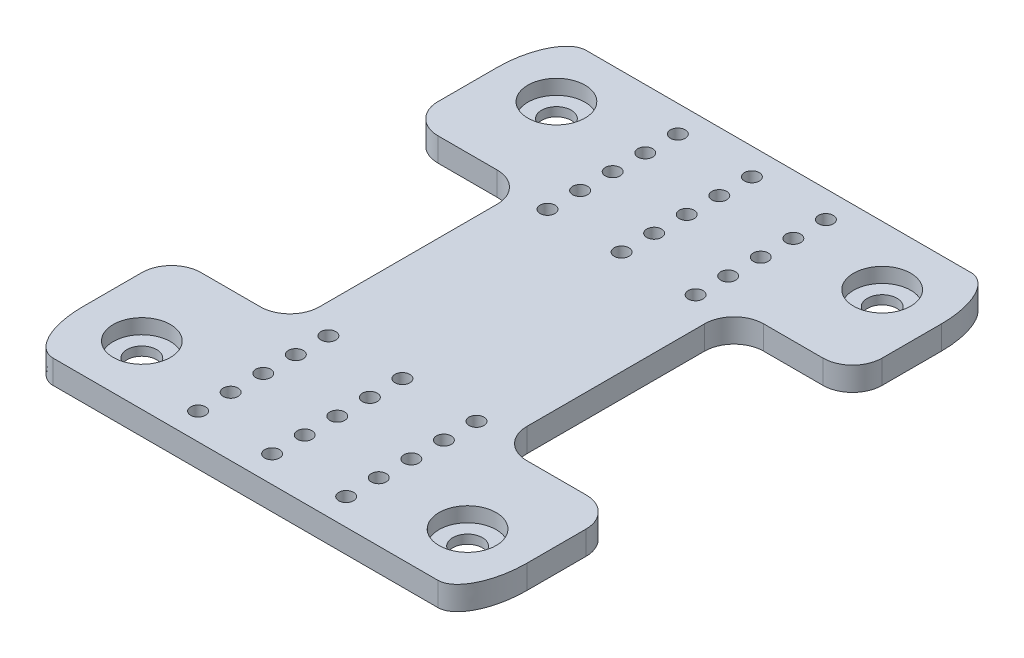
SolidWorks part; units mm, degrees
ref_plane "Front Plane" through (0, 0, 0) normal (0, 0, 1) x (1, 0, 0)
ref_plane "Top Plane" through (0, 0, 0) normal (0, 1, 0) x (1, 0, 0)
ref_plane "Right Plane" through (0, 0, 0) normal (1, 0, 0) x (0, 0, -1)
sketch "Sketch2" plane through (0, 0, 0) normal (0, 1, 0) x (1, 0, 0)
  line L1 (-75, 90) -> (75, 90)
  line L2 (-75, 90) -> (-75, -90)
  line L3 (-75, -90) -> (75, -90)
  line L4 (75, 90) -> (75, -90)
  line L5 (-75, 90) -> (75, -90) construction
  line L6 (-75, -90) -> (75, 90) construction
  point P0 (0, 0)
  dimension "D1" = 150
  dimension "D2" = 180
extrude "Boss-Extrude1" add sketch "Sketch2" along normal mid plane 8
sketch "Sketch3" plane through (0, 4, 0) normal (0, 1, 0) x (1, 0, 0)
  line L15 (-75, 90) -> (-75, -90) construction
  line L16 (-75, -90) -> (75, -90) construction
  circle A4 centre (-55, -70) radius 9.65
  dimension "D1" = 19.3
  dimension "D3" = 20
  dimension "D2" = 20
fillet "Fillet1" radius 10 2 edges at (-75, 0, -90) (75, 0, 90) second distance 20 first distance on face at (0, 0, -90) first distance on face at (0, 0, 90)
fillet "Fillet2" radius 20 2 edges at (75, 0, -90) (-75, 0, 90) second distance 10 first distance on face at (75, 1, 30) first distance on face at (-75, 1, -30)
extrude "Cut-Extrude1" cut sketch "Sketch3" against normal blind 5 contours A4
sketch "Sketch7" plane through (0, 4, 0) normal (0, 1, 0) x (1, 0, 0)
  circle A1 centre (-55, -70) radius 5
  dimension "D1" = 10
extrude "Cut-Extrude4" cut sketch "Sketch7" against normal through all
mirror "Mirror1" about plane through (0, 0, 0) normal (0, 0, 1) of "Cut-Extrude4", "Cut-Extrude1"
mirror "Mirror2" about plane through (0, 0, 0) normal (1, 0, 0) of "Cut-Extrude4", "Mirror1"
sketch "Sketch4" plane through (0, 4, 0) normal (0, 1, 0) x (1, 0, 0)
  line L0 (-75, 70) -> (-75, -70) construction
  line L1 (-115, 40) -> (-35, 40)
  line L2 (-115, 40) -> (-115, -40)
  line L3 (-115, -40) -> (-35, -40)
  line L4 (-35, 40) -> (-35, -40)
  line L5 (-115, 40) -> (-35, -40) construction
  line L6 (-115, -40) -> (-35, 40) construction
  point P0 (-75, 0)
  dimension "D1" = 80
  dimension "D2" = 40
extrude "Cut-Extrude2" cut sketch "Sketch4" against normal through all
mirror "Mirror3" about plane through (0, 0, 0) normal (1, 0, 0) of "Cut-Extrude2"
fillet "Fillet3" radius 10 8 edges at (75, 0, -40) (75, 0, 40) (-75, 0, -40) (-75, 0, 40) (-35, 0, -40) (-35, 0, 40) (35, 0, 40) (35, 0, -40)
sketch "Sketch6" plane through (0, 4, 0) normal (0, 1, 0) x (1, 0, 0)
  line L0 (-25, 81) -> (25, 81) construction
  line L1 (65, 90) -> (-65, 90) construction
  circle A0 centre (-25, 81) radius 2.5
  circle A1 centre (25, 81) radius 2.5
  circle A2 centre (0, 81) radius 2.5
  circle A3 centre (-25, 70) radius 2.5
  circle A4 centre (0, 70) radius 2.5
  circle A5 centre (25, 70) radius 2.5
  circle A6 centre (-25, 59) radius 2.5
  circle A7 centre (0, 59) radius 2.5
  circle A8 centre (25, 59) radius 2.5
  circle A9 centre (-25, 48) radius 2.5
  circle A10 centre (0, 48) radius 2.5
  circle A11 centre (25, 48) radius 2.5
  circle A12 centre (-25, 37) radius 2.5
  circle A13 centre (0, 37) radius 2.5
  circle A14 centre (25, 37) radius 2.5
  point P4 (0, 81)
  point P7 (0, 90)
  dimension "D1" = 5
  dimension "D2" = 9
  dimension "D3" = 50
  dimension "D4" = 5
extrude "Cut-Extrude3" cut sketch "Sketch6" against normal through all
mirror "Mirror4" about plane through (0, 0, 0) normal (0, 0, 1) of "Cut-Extrude3"
